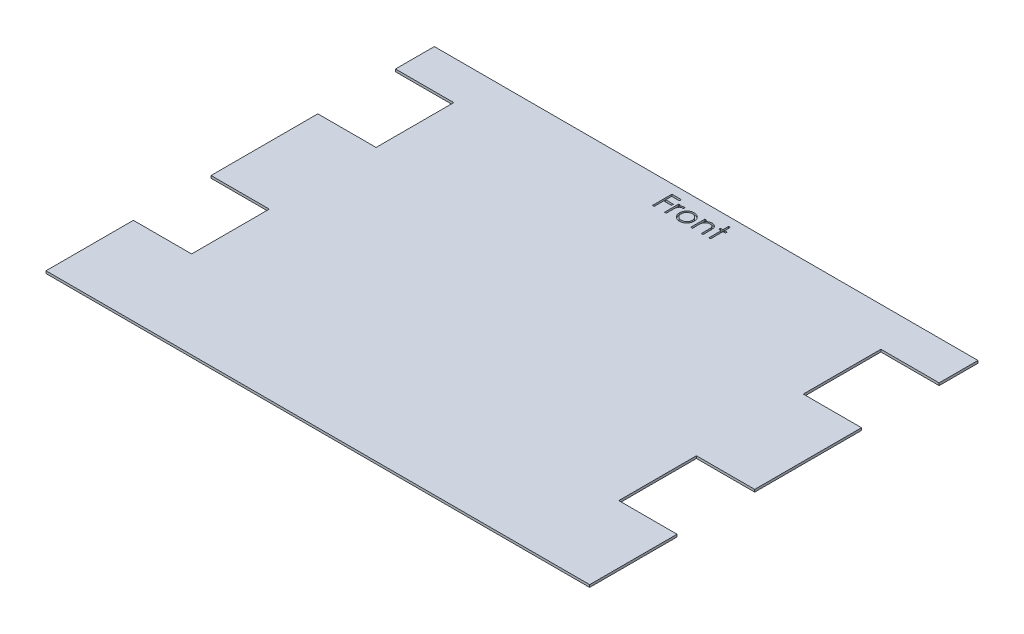
SolidWorks part; units mm, degrees
ref_plane "Front Plane" through (0, 0, 0) normal (0, 0, 1) x (1, 0, 0)
ref_plane "Top Plane" through (0, 0, 0) normal (0, 1, 0) x (1, 0, 0)
ref_plane "Right Plane" through (0, 0, 0) normal (1, 0, 0) x (0, 0, -1)
sketch "Sketch1" plane through (0, 0, 0) normal (0, 1, 0) x (1, 0, 0)
  line L0 (-355.6, 254) -> (355.6, -254) construction
  line L1 (-279.4, 152.4) -> (-82.55, 152.4) construction
  line L2 (-355.6, 203.2) -> (-279.4, 203.2)
  line L3 (355.6, 190.5) -> (82.55, 190.5) construction
  line L4 (355.6, 203.2) -> (355.6, 101.6) construction
  line L5 (355.6, 114.3) -> (82.55, 114.3) construction
  line L6 (82.55, 190.5) -> (82.55, 114.3) construction
  line L7 (355.6, -50.8) -> (82.55, -50.8) construction
  line L8 (355.6, -38.1) -> (355.6, -139.7) construction
  line L9 (355.6, -127) -> (82.55, -127) construction
  line L10 (82.55, -50.8) -> (82.55, -127) construction
  line L11 (-355.6, -50.8) -> (-82.55, -50.8) construction
  line L12 (-355.6, -38.1) -> (-355.6, -139.7) construction
  line L13 (-355.6, -127) -> (-82.55, -127) construction
  line L14 (-82.55, -50.8) -> (-82.55, -127) construction
  line L15 (-355.6, 190.5) -> (-82.55, 190.5) construction
  line L16 (-355.6, 203.2) -> (-355.6, 101.6) construction
  line L17 (-355.6, 114.3) -> (-82.55, 114.3) construction
  line L18 (-355.6, 254) -> (355.6, 254)
  line L19 (-355.6, 254) -> (-355.6, 203.2)
  line L20 (-355.6, -254) -> (355.6, -254)
  line L21 (355.6, 254) -> (355.6, 203.2)
  line L22 (-82.55, 190.5) -> (-82.55, 114.3) construction
  line L23 (355.6, 101.6) -> (355.6, -38.1)
  line L24 (-355.6, 101.6) -> (-279.4, 101.6)
  line L25 (-279.4, 203.2) -> (-279.4, 101.6)
  line L26 (-355.6, -38.1) -> (-279.4, -38.1)
  line L27 (355.6, -139.7) -> (355.6, -254)
  line L28 (-355.6, -139.7) -> (-279.4, -139.7)
  line L29 (-279.4, -38.1) -> (-279.4, -139.7)
  line L30 (279.4, -38.1) -> (355.6, -38.1)
  line L31 (279.4, -38.1) -> (279.4, -139.7)
  line L32 (279.4, -139.7) -> (355.6, -139.7)
  line L34 (355.6, 101.6) -> (279.4, 101.6)
  line L35 (-279.4, -88.9) -> (-82.55, -88.9) construction
  line L36 (355.6, 203.2) -> (279.4, 203.2)
  line L37 (279.4, 101.6) -> (279.4, 203.2)
  line L38 (-355.6, 101.6) -> (-355.6, -38.1)
  line L39 (-355.6, -139.7) -> (-355.6, -254)
  dimension "D1" = 273.05
  dimension "D2" = 76.2
  dimension "D3" = 101.6
  dimension "D4" = 127
  dimension "D5" = 101.6
  dimension "D6" = 711.2
  dimension "D7" = 508
  dimension "D8" = 76.2
extrude "Boss-Extrude1" add sketch "Sketch1" along normal blind 3.175
sketch "Sketch2" plane through (0, 3.175, 0) normal (0, 1, 0) x (1, 0, 0)
  line L0 (-355.6, 254) -> (-355.6, 203.2) construction
  line L1 (-355.6, 190.5) -> (-82.55, 190.5) construction
  line L2 (-355.6, 190.5) -> (-355.6, 114.3) construction
  line L3 (-355.6, 114.3) -> (-82.55, 114.3) construction
  line L4 (-82.55, 190.5) -> (-82.55, 114.3) construction
  line L5 (355.6, 203.2) -> (355.6, 254) construction
  line L6 (-355.6, -50.8) -> (-82.55, -50.8) construction
  line L7 (-355.6, -50.8) -> (-355.6, -127) construction
  line L8 (-355.6, -127) -> (-82.55, -127) construction
  line L9 (-82.55, -50.8) -> (-82.55, -127) construction
  line L10 (355.6, -127) -> (82.55, -127) construction
  line L11 (355.6, -127) -> (355.6, -50.8) construction
  line L12 (355.6, -50.8) -> (82.55, -50.8) construction
  line L13 (82.55, -127) -> (82.55, -50.8) construction
  line L15 (355.6, 114.3) -> (82.55, 114.3) construction
  line L16 (355.6, 114.3) -> (355.6, 190.5) construction
  line L17 (355.6, 190.5) -> (82.55, 190.5) construction
  line L18 (82.55, 114.3) -> (82.55, 190.5) construction
  line L19 (-355.6, -254) -> (355.6, -254) construction
  line L20 (-355.6, 152.4) -> (-82.55, 152.4) construction
  line L21 (355.6, 254) -> (-355.6, 254) construction
  dimension "D1" = 273.05
  dimension "D2" = 76.2
  dimension "D3" = 101.6
  dimension "D4" = 127
sketch "Sketch3" plane through (0, 3.175, 0) normal (0, 1, 0) x (1, 0, 0)
  text T0 "Front" font "Century Gothic" height 25.4
extrude "Cut-Extrude1" cut sketch "Sketch3" against normal blind 2.54
